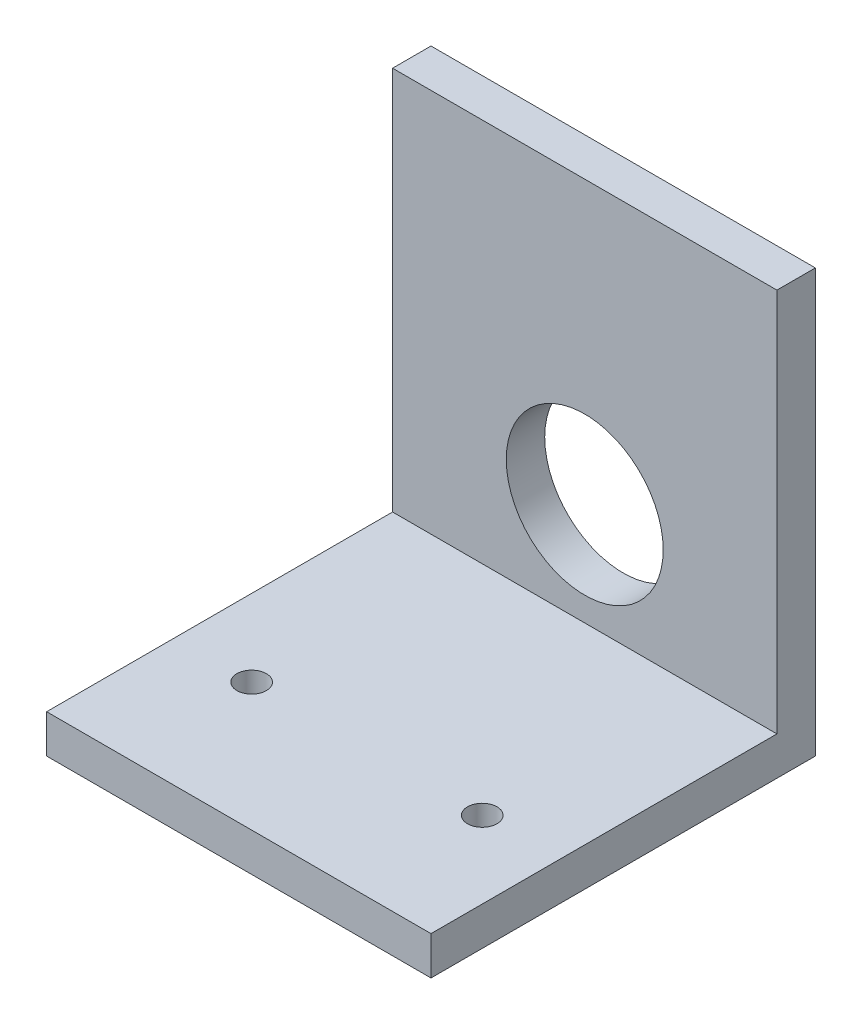
SolidWorks part; units mm, degrees
ref_plane "Front Plane" through (0, 0, 0) normal (0, 0, 1) x (1, 0, 0)
ref_plane "Top Plane" through (0, 0, 0) normal (0, 1, 0) x (1, 0, 0)
ref_plane "Right Plane" through (0, 0, 0) normal (1, 0, 0) x (0, 0, -1)
sketch "Sketch1" plane through (0, 0, 0) normal (0, 1, 0) x (1, 0, 0)
  line L1 (0, 0) -> (30, 0)
  line L2 (0, 0) -> (0, 30)
  line L3 (0, 30) -> (30, 30)
  line L4 (30, 0) -> (30, 30)
  circle A0 centre (6, 10) radius 1.15
  circle A1 centre (24, 10) radius 1.15
  dimension "D2" = 2.3
  dimension "D3" = 2.3
  dimension "D4" = 18
  dimension "D7" = 20
  dimension "D1" = 30
  dimension "D5" = 6
  dimension "D6" = 30
extrude "Boss-Extrude1" add sketch "Sketch1" along normal blind 3
sketch "Sketch2" plane through (0, 3, 0) normal (0, 1, 0) x (1, 0, 0)
  line L0 (0, 30) -> (0, 0) construction
  line L1 (30, 30) -> (0, 30)
  line L2 (30, 30) -> (30, 27)
  line L3 (30, 27) -> (0, 27)
  line L4 (0, 30) -> (0, 27)
  dimension "D1" = 3
extrude "Boss-Extrude2" add sketch "Sketch2" along normal blind 30
sketch "Sketch3" plane through (0, 0, -30) normal (0, 0, -1) x (-1, 0, 0)
  line L0 (-30, 0) -> (0, 0) construction
  line L1 (-30, 33) -> (-30, 0) construction
  circle A0 centre (-15, 11) radius 6.125
  dimension "D1" = 11
  dimension "D2" = 12.25
  dimension "D3" = 15
extrude "Cut-Extrude1" cut sketch "Sketch3" against normal up to next
